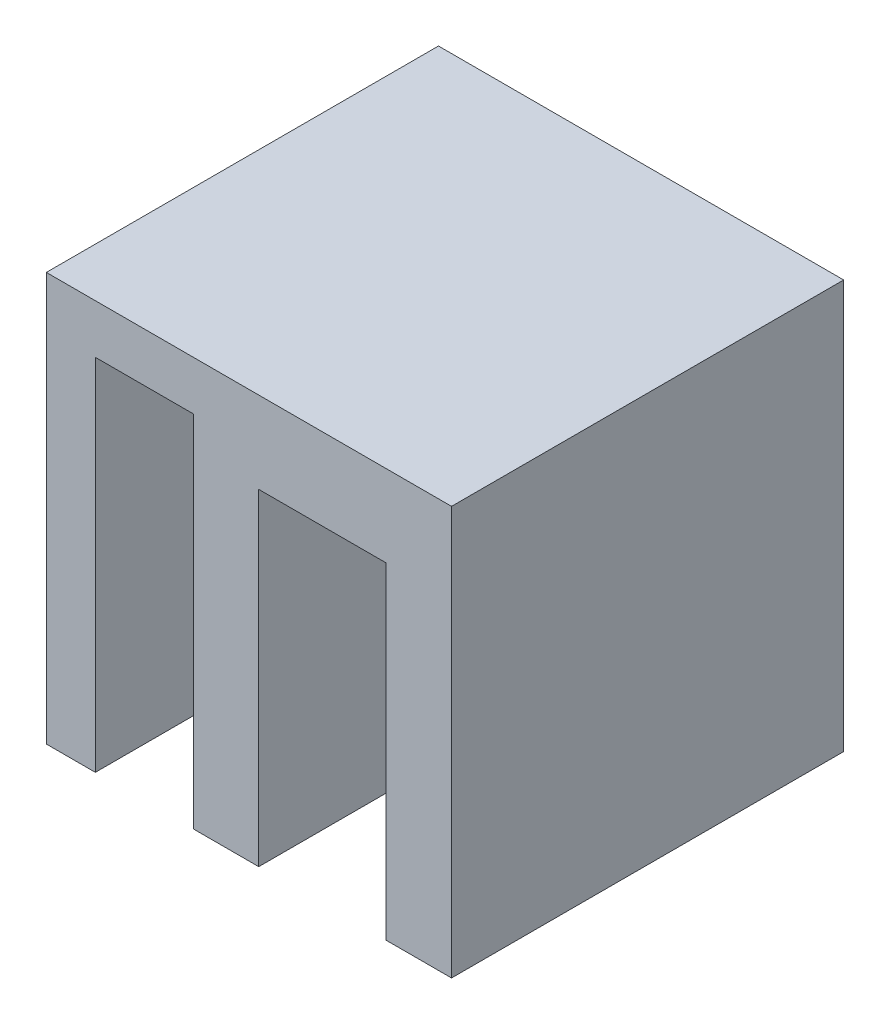
SolidWorks part; units mm, degrees
ref_plane "Front Plane" through (0, 0, 0) normal (0, 0, 1) x (1, 0, 0)
ref_plane "Top Plane" through (0, 0, 0) normal (0, 1, 0) x (1, 0, 0)
ref_plane "Right Plane" through (0, 0, 0) normal (1, 0, 0) x (0, 0, -1)
sketch "Sketch1" plane through (0, 0, 0) normal (0, 0, 1) x (1, 0, 0)
  line L0 (0, 0) -> (45.9503, 0) construction
  line L1 (0, 0) -> (0, -43.168) construction
  line L2 (-3.9, 0) -> (-3.9, -43.168) construction
  line L3 (-3.9, -10) -> (-3.9, 0)
  line L4 (-3.9, 0) -> (0, 0)
  line L5 (0, 0) -> (0, -10)
  line L6 (0, -10) -> (2, -10)
  line L7 (2, -10) -> (2, 2.5)
  line L8 (2, 2.5) -> (-5, 2.5)
  line L9 (-5.9, 1) -> (-5.9, -10)
  line L10 (-5.9, -10) -> (-3.9, -10)
  line L11 (-8, 2.5) -> (-10.4, 2.5)
  line L12 (-5, 2.5) -> (-8, 2.5)
  line L14 (-5.9, 1) -> (-7, 1)
  line L24 (-10.4, 2.5) -> (-10.4, -10)
  line L28 (-8.9, -1) -> (-8.9, 1)
  line L29 (-8.9, 1) -> (-7, 1)
  line L30 (-8.9, -1) -> (-8.9, -10)
  line L31 (-10.4, -10) -> (-8.9, -10)
  dimension "D2" = 2
  dimension "D3" = 2.5
  dimension "D4" = 2
  dimension "D5" = 10
  dimension "D6" = 10
  dimension "D7" = 3
  dimension "D8" = 2
  dimension "D9" = 1.5
  dimension "D12" = 1.5
  dimension "D1" = 3.9
extrude "Boss-Extrude1" add sketch "Sketch1" along normal blind 12
